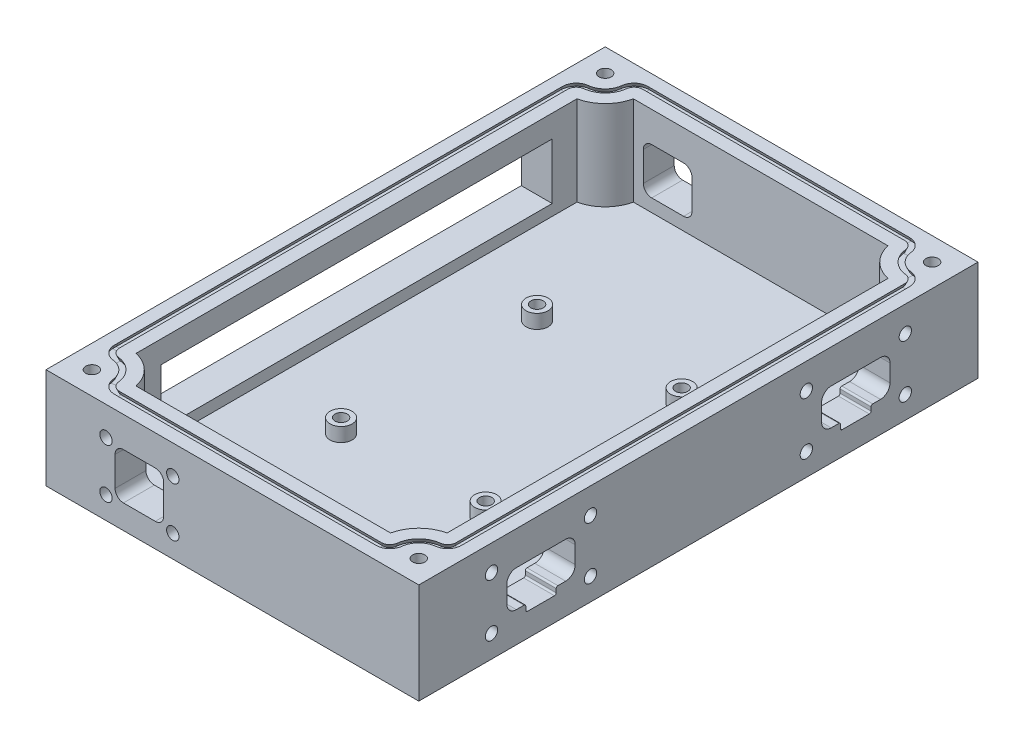
SolidWorks part; units mm, degrees
note: The reader was unsure of these and kept them because the rebuilt part matched: shared geometry of "Sketch5<2>", "Sketch6<2>".
ref_plane "Front Plane" through (0, 0, 0) normal (0, 0, 1) x (1, 0, 0)
ref_plane "Top Plane" through (0, 0, 0) normal (0, 1, 0) x (1, 0, 0)
ref_plane "Right Plane" through (0, 0, 0) normal (1, 0, 0) x (0, 0, -1)
sketch "Sketch1" plane through (0, 0, 0) normal (0, 1, 0) x (1, 0, 0)
  line L1 (0, 0) -> (169.3418, 0)
  line L2 (0, 0) -> (0, 254)
  line L3 (0, 254) -> (169.3418, 254)
  line L4 (169.3418, 0) -> (169.3418, 254)
  dimension "D1" = 169.3418
  dimension "D2" = 254
extrude "Boss-Extrude1" add sketch "Sketch1" along normal blind 45.72
sketch "12 pin hole" [suppressed] plane through (254, 0, 0) normal (1, 0, 0) x (0, 0, -1)
  line L8 (50.8, 10.16) -> (95.758, 10.16) construction
  line L9 (50.8, 10.16) -> (50.8, 34.036) construction
  line L10 (50.8, 34.036) -> (95.758, 34.036) construction
  line L11 (95.758, 10.16) -> (95.758, 34.036) construction
  line L12 (55.7357, 28.956) -> (54.2925, 28.956)
  line L13 (52.7685, 27.432) -> (52.7685, 16.764)
  line L14 (54.2925, 15.24) -> (55.7357, 15.24)
  line L16 (90.087, 29.972) -> (92.2655, 29.972)
  line L17 (93.7895, 28.448) -> (93.7895, 15.748)
  line L18 (92.2655, 14.224) -> (90.087, 14.224)
  line L21 (62.4205, 25.654) -> (84.1375, 25.654) construction
  line L22 (62.4205, 25.654) -> (62.4205, 18.542) construction
  line L23 (62.4205, 18.542) -> (84.1375, 18.542) construction
  line L24 (84.1375, 25.654) -> (84.1375, 18.542) construction
  line L25 (62.4205, 32.7152) -> (84.1375, 32.7152)
  line L26 (62.4205, 11.4808) -> (84.1375, 11.4808)
  line L27 (52.7685, 22.098) -> (50.8, 22.098) construction
  line L28 (93.7895, 22.098) -> (95.758, 22.098) construction
  arc A4 (62.4205, 32.7152) -> (56.3868, 29.3222) centre (62.4205, 25.654) ccw
  arc A5 (89.5075, 30.2392) -> (84.1375, 32.7152) centre (84.1375, 25.654) ccw
  arc A6 (62.4205, 11.4808) -> (56.3868, 14.8738) centre (62.4205, 18.542) cw
  arc A7 (89.5075, 13.9568) -> (84.1375, 11.4808) centre (84.1375, 18.542) cw
  arc A8 (90.087, 29.972) -> (89.5075, 30.2392) centre (90.087, 30.734) cw
  arc A9 (90.087, 14.224) -> (89.5075, 13.9568) centre (90.087, 13.462) ccw
  arc A10 (55.7357, 15.24) -> (56.3868, 14.8738) centre (55.7357, 14.478) cw
  arc A11 (55.7357, 28.956) -> (56.3868, 29.3222) centre (55.7357, 29.718) ccw
  arc A12 (92.2655, 29.972) -> (93.7895, 28.448) centre (92.2655, 28.448) cw
  arc A13 (93.7895, 15.748) -> (92.2655, 14.224) centre (92.2655, 15.748) cw
  arc A14 (52.7685, 16.764) -> (54.2925, 15.24) centre (54.2925, 16.764) ccw
  arc A15 (54.2925, 28.956) -> (52.7685, 27.432) centre (54.2925, 27.432) ccw
  point P25 (50.8, 22.098)
  point P28 (52.7685, 22.098)
  point P29 (93.7895, 22.098)
  point P34 (62.4205, 22.098)
  point P35 (84.1375, 22.098)
  point P44 (73.279, 10.16)
  point P46 (73.279, 11.4808)
  point P59 (93.7895, 29.972)
  point P62 (93.7895, 14.224)
  point P65 (52.7685, 15.24)
  point P68 (52.7685, 28.956)
  dimension "D4" = 41.021
  dimension "D5" = 15.748
  dimension "D11" = 7.0612
  dimension "D12" = 0.762
  dimension "D13" = 1.524
  dimension "D1" = 44.958
  dimension "D2" = 23.876
  dimension "D8" = 13.716
  dimension "D9" = 21.2344
  dimension "D10" = 21.717
sketch "Sketch2" plane through (0, 45.72, 0) normal (0, 1, 0) x (1, 0, 0)
  line L0 (84.6709, 14.0292) -> (84.6709, 0) construction
  line L5 (0, 10.42) -> (10.42, 10.42) construction
  line L6 (14.0292, 239.9708) -> (155.3126, 239.9708)
  line L7 (10.42, 10.42) -> (10.42, 0) construction
  line L16 (14.0292, 239.9708) -> (14.0292, 14.0292)
  line L17 (14.0292, 14.0292) -> (155.3126, 14.0292)
  line L18 (155.3126, 239.9708) -> (155.3126, 14.0292)
  line L19 (0, 0) -> (169.3418, 0) construction
  line L20 (158.9218, 0) -> (158.9218, 10.42) construction
  line L21 (14.0292, 127) -> (0, 127) construction
  line L22 (0, 254) -> (0, 0) construction
  line L23 (158.9218, 10.42) -> (169.3418, 10.42) construction
  line L24 (169.3418, 0) -> (169.3418, 254) construction
  line L25 (25.2202, 246.9854) -> (144.1216, 246.9854)
  line L38 (7.0146, 228.7798) -> (7.0146, 25.2202)
  line L47 (25.2202, 7.0146) -> (144.1216, 7.0146)
  line L48 (162.3272, 228.7798) -> (162.3272, 25.2202)
  line L49 (169.3418, 243.58) -> (158.9218, 243.58) construction
  line L50 (158.9218, 243.58) -> (158.9218, 254) construction
  line L51 (169.3418, 254) -> (0, 254) construction
  line L52 (0, 243.58) -> (10.42, 243.58) construction
  line L53 (10.42, 243.58) -> (10.42, 254) construction
  line L54 (10.42, 10.42) -> (17.36, 17.36) construction
  line L55 (17.36, 17.36) -> (22.3201, 22.3201) construction
  line L56 (158.9218, 10.42) -> (151.9818, 17.36) construction
  line L57 (151.9818, 17.36) -> (147.0217, 22.3201) construction
  line L58 (158.9218, 243.58) -> (151.9818, 236.64) construction
  line L59 (151.9818, 236.64) -> (147.0217, 231.6799) construction
  line L60 (10.42, 243.58) -> (17.36, 236.64) construction
  line L61 (17.36, 236.64) -> (22.3201, 231.6799) construction
  line L62 (155.3126, 127) -> (169.3418, 127) construction
  line L63 (84.6709, 239.9708) -> (84.6709, 254) construction
  arc A13 (26.8577, 14.0292) -> (14.0292, 26.8577) centre (10.42, 10.42) ccw
  arc A14 (14.0292, 227.1423) -> (26.8577, 239.9708) centre (10.42, 243.58) ccw
  arc A15 (142.4841, 239.9708) -> (155.3126, 227.1423) centre (158.9218, 243.58) ccw
  arc A16 (155.3126, 26.8577) -> (142.4841, 14.0292) centre (158.9218, 10.42) ccw
  arc A17 (157.8183, 20.1724) -> (149.1694, 11.5235) centre (158.9218, 10.42) ccw
  arc A18 (149.1694, 242.4765) -> (157.8183, 233.8276) centre (158.9218, 243.58) ccw
  arc A19 (11.5235, 233.8276) -> (20.1724, 242.4765) centre (10.42, 243.58) ccw
  arc A20 (20.1724, 11.5235) -> (11.5235, 20.1724) centre (10.42, 10.42) ccw
  arc A21 (25.2202, 7.0146) -> (20.1724, 11.5235) centre (25.2202, 12.0946) cw
  arc A22 (149.1694, 11.5235) -> (144.1216, 7.0146) centre (144.1216, 12.0946) cw
  arc A23 (162.3272, 25.2202) -> (157.8183, 20.1724) centre (157.2472, 25.2202) cw
  arc A24 (162.3272, 228.7798) -> (157.8183, 233.8276) centre (157.2472, 228.7798) ccw
  arc A25 (149.1694, 242.4765) -> (144.1216, 246.9854) centre (144.1216, 241.9054) ccw
  arc A26 (25.2202, 246.9854) -> (20.1724, 242.4765) centre (25.2202, 241.9054) ccw
  arc A27 (11.5235, 233.8276) -> (7.0146, 228.7798) centre (12.0946, 228.7798) ccw
  arc A28 (11.5235, 20.1724) -> (7.0146, 25.2202) centre (12.0946, 25.2202) cw
  point P12 (84.6709, 7.0146)
  point P17 (84.6709, 7.0146)
  point P18 (7.0146, 127)
  point P85 (84.6709, 246.9854)
  point P86 (84.6709, 246.9854)
  point P87 (162.3272, 127)
  point P88 (162.3272, 127)
  point P89 (10.42, 243.58)
  point P90 (7.0146, 127)
  point P91 (10.42, 10.42)
  point P92 (158.9218, 10.42)
  point P93 (158.9218, 243.58)
  dimension "D2" = 9.8146
  dimension "D1" = 7.0146
  dimension "D3" = 10.42
  dimension "D4" = 7.0146
extrude "Cut-Extrude1" cut sketch "Sketch2" against normal offset from surface (40.64 mm away) 5.08
ref_plane "groove plane" through (14.0292, 45.72, -26.8577) normal (0, 0, 1) x (1, 0, 0)
sketch "Sketch3" plane through (0, 45.72, 0) normal (0, 1, 0) x (1, 0, 0)
  line L64 (25.2202, 246.9854) -> (144.1216, 246.9854) construction
  line L65 (162.3272, 228.7798) -> (162.3272, 25.2202) construction
  line L66 (25.2202, 7.0146) -> (144.1216, 7.0146) construction
  line L67 (7.0146, 228.7798) -> (7.0146, 25.2202) construction
  line L68 (25.2202, 246.9854) -> (144.1216, 246.9854)
  line L69 (162.3272, 228.7798) -> (162.3272, 25.2202)
  line L70 (25.2202, 7.0146) -> (144.1216, 7.0146)
  line L71 (7.0146, 228.7798) -> (7.0146, 25.2202)
  arc A40 (149.1694, 242.4765) -> (144.1216, 246.9854) centre (144.1216, 241.9054) ccw construction
  arc A41 (149.1694, 242.4765) -> (157.8183, 233.8276) centre (158.9218, 243.58) ccw construction
  arc A42 (162.3272, 228.7798) -> (157.8183, 233.8276) centre (157.2472, 228.7798) ccw construction
  arc A43 (157.8183, 20.1724) -> (162.3272, 25.2202) centre (157.2472, 25.2202) ccw construction
  arc A44 (157.8183, 20.1724) -> (149.1694, 11.5235) centre (158.9218, 10.42) ccw construction
  arc A45 (144.1216, 7.0146) -> (149.1694, 11.5235) centre (144.1216, 12.0946) ccw construction
  arc A46 (20.1724, 11.5235) -> (25.2202, 7.0146) centre (25.2202, 12.0946) ccw construction
  arc A47 (20.1724, 11.5235) -> (11.5235, 20.1724) centre (10.42, 10.42) ccw construction
  arc A48 (7.0146, 25.2202) -> (11.5235, 20.1724) centre (12.0946, 25.2202) ccw construction
  arc A49 (11.5235, 233.8276) -> (7.0146, 228.7798) centre (12.0946, 228.7798) ccw construction
  arc A50 (11.5235, 233.8276) -> (20.1724, 242.4765) centre (10.42, 243.58) ccw construction
  arc A51 (25.2202, 246.9854) -> (20.1724, 242.4765) centre (25.2202, 241.9054) ccw construction
  arc A52 (149.1694, 242.4765) -> (144.1216, 246.9854) centre (144.1216, 241.9054) ccw
  arc A53 (149.1694, 242.4765) -> (157.8183, 233.8276) centre (158.9218, 243.58) ccw
  arc A54 (162.3272, 228.7798) -> (157.8183, 233.8276) centre (157.2472, 228.7798) ccw
  arc A55 (157.8183, 20.1724) -> (162.3272, 25.2202) centre (157.2472, 25.2202) ccw
  arc A56 (157.8183, 20.1724) -> (149.1694, 11.5235) centre (158.9218, 10.42) ccw
  arc A57 (144.1216, 7.0146) -> (149.1694, 11.5235) centre (144.1216, 12.0946) ccw
  arc A58 (20.1724, 11.5235) -> (25.2202, 7.0146) centre (25.2202, 12.0946) ccw
  arc A59 (20.1724, 11.5235) -> (11.5235, 20.1724) centre (10.42, 10.42) ccw
  arc A60 (7.0146, 25.2202) -> (11.5235, 20.1724) centre (12.0946, 25.2202) ccw
  arc A61 (11.5235, 233.8276) -> (7.0146, 228.7798) centre (12.0946, 228.7798) ccw
  arc A62 (11.5235, 233.8276) -> (20.1724, 242.4765) centre (10.42, 243.58) ccw
  arc A63 (25.2202, 246.9854) -> (20.1724, 242.4765) centre (25.2202, 241.9054) ccw
sketch "Sketch4" plane through (6.1853, 0, -26.8577) normal (0, 0, 1) x (1, 0, 0)
  line L0 (-0.3137, 45.72) -> (-1.1053, 43.942)
  line L1 (1.9723, 45.72) -> (2.764, 43.942)
  line L2 (-1.1053, 43.942) -> (2.764, 43.942)
  line L5 (-0.3137, 45.72) -> (1.9723, 45.72)
  point P5 (0.8293, 45.72)
  dimension "D1" = 1.778
  dimension "D3" = 66
  dimension "D4" = 66
  dimension "D2" = 3.8692
sweep "Cut-Sweep2" cut profiles "Sketch4" path "Sketch3"
sketch "Sketch14" plane through (0, 45.72, 0) normal (0, 1, 0) x (1, 0, 0)
  circle A0 centre (10.42, 243.58) radius 2.8
  circle A1 centre (158.9218, 243.58) radius 2.8
  circle A2 centre (158.9218, 10.42) radius 2.8
  circle A3 centre (10.42, 10.42) radius 2.8
  dimension "D1" = 5.6
extrude "Cut-Extrude11" cut sketch "Sketch14" against normal blind 5.5
sketch "Sketch13" plane through (169.3418, 0, 0) normal (1, 0, 0) x (0, 0, -1)
  line L0 (33.02, 10.16) -> (33.02, 0) construction
  line L1 (0, 0) -> (254, 0) construction
  line L2 (33.02, 10.16) -> (0, 10.16) construction
  line L3 (0, 45.72) -> (0, 0) construction
  line L4 (220.98, 0) -> (220.98, 10.16) construction
  line L5 (220.98, 10.16) -> (254, 10.16) construction
  line L6 (254, 45.72) -> (254, 0) construction
  line B0 (48.5902, 13.0937) -> (48.5902, 11.4173)
  line B1 (33.02, 34.036) -> (77.978, 34.036) construction
  line B2 (33.02, 34.036) -> (33.02, 10.16) construction
  line B3 (33.02, 10.16) -> (77.978, 10.16) construction
  line B4 (77.978, 34.036) -> (77.978, 10.16) construction
  line B5 (44.2976, 30.3403) -> (66.7004, 30.3403)
  line B6 (39.9542, 25.9969) -> (39.9542, 18.1991)
  line B7 (44.2976, 13.8557) -> (47.8282, 13.8557)
  line B8 (71.0438, 25.9969) -> (71.0438, 18.1991)
  line B9 (39.9542, 30.3403) -> (71.0438, 13.8557) construction
  line B10 (39.9542, 13.8557) -> (71.0438, 30.3403) construction
  line B11 (49.3522, 10.6553) -> (61.6458, 10.6553)
  line B12 (62.4078, 11.4173) -> (62.4078, 13.0937)
  line B13 (63.1698, 13.8557) -> (66.7004, 13.8557)
  arc B14 (66.7004, 13.8557) -> (71.0438, 18.1991) centre (66.7004, 18.1991) ccw
  arc B15 (39.9542, 18.1991) -> (44.2976, 13.8557) centre (44.2976, 18.1991) ccw
  arc B16 (66.7004, 30.3403) -> (71.0438, 25.9969) centre (66.7004, 25.9969) cw
  arc B17 (44.2976, 30.3403) -> (39.9542, 25.9969) centre (44.2976, 25.9969) ccw
  arc B18 (62.4078, 13.0937) -> (63.1698, 13.8557) centre (63.1698, 13.0937) cw
  arc B19 (61.6458, 10.6553) -> (62.4078, 11.4173) centre (61.6458, 11.4173) ccw
  arc B20 (48.5902, 11.4173) -> (49.3522, 10.6553) centre (49.3522, 11.4173) ccw
  arc B21 (48.5902, 13.0937) -> (47.8282, 13.8557) centre (47.8282, 13.0937) ccw
  line B22 (191.5922, 13.0937) -> (191.5922, 11.4173)
  line B23 (176.022, 34.036) -> (220.98, 34.036) construction
  line B24 (176.022, 34.036) -> (176.022, 10.16) construction
  line B25 (176.022, 10.16) -> (220.98, 10.16) construction
  line B26 (220.98, 34.036) -> (220.98, 10.16) construction
  line B27 (187.2996, 30.3403) -> (209.7024, 30.3403)
  line B28 (182.9562, 25.9969) -> (182.9562, 18.1991)
  line B29 (187.2996, 13.8557) -> (190.8302, 13.8557)
  line B30 (214.0458, 25.9969) -> (214.0458, 18.1991)
  line B31 (182.9562, 30.3403) -> (214.0458, 13.8557) construction
  line B32 (182.9562, 13.8557) -> (214.0458, 30.3403) construction
  line B33 (192.3542, 10.6553) -> (204.6478, 10.6553)
  line B34 (205.4098, 11.4173) -> (205.4098, 13.0937)
  line B35 (206.1718, 13.8557) -> (209.7024, 13.8557)
  arc B36 (209.7024, 13.8557) -> (214.0458, 18.1991) centre (209.7024, 18.1991) ccw
  arc B37 (182.9562, 18.1991) -> (187.2996, 13.8557) centre (187.2996, 18.1991) ccw
  arc B38 (209.7024, 30.3403) -> (214.0458, 25.9969) centre (209.7024, 25.9969) cw
  arc B39 (187.2996, 30.3403) -> (182.9562, 25.9969) centre (187.2996, 25.9969) ccw
  arc B40 (205.4098, 13.0937) -> (206.1718, 13.8557) centre (206.1718, 13.0937) cw
  arc B41 (204.6478, 10.6553) -> (205.4098, 11.4173) centre (204.6478, 11.4173) ccw
  arc B42 (191.5922, 11.4173) -> (192.3542, 10.6553) centre (192.3542, 11.4173) ccw
  arc B43 (191.5922, 13.0937) -> (190.8302, 13.8557) centre (190.8302, 13.0937) ccw
  dimension "D1" = 33.02
  dimension "D2" = 10.16
sketch_block_instance "Block7-3"
sketch_block "Block7" parameters "D6"=4.3434, "D7"=0.762, "D1"=44.958, "D2"=23.876, "D3"=31.0896, "D4"=16.4846, "D5"=19.685
sketch_block_instance "Block7-4"
extrude "Cut-Extrude10" cut sketch "Sketch13" against normal up to next
sketch "12 pin mount" plane through (169.3418, 0, 0) normal (1, 0, 0) x (0, 0, -1)
  circle A0 centre (77.978, 34.036) radius 2.8
  circle A1 centre (176.022, 10.16) radius 2.8
  circle A2 centre (33.02, 10.16) radius 2.8
  circle A3 centre (77.978, 10.16) radius 2.8
  circle A5 centre (220.98, 34.036) radius 2.8
  circle A6 centre (220.98, 10.16) radius 2.8
  circle A7 centre (176.022, 34.036) radius 2.8
  circle A8 centre (33.02, 34.036) radius 2.8
  dimension "D1" = 5.6
extrude "Cut-Extrude3" cut sketch "12 pin mount" against normal blind 5.5
sketch "4 pin connector" plane through (0, 0, 0) normal (0, 0, 1) x (1, 0, 0)
  line L0 (57.5818, 0) -> (57.5818, 10.16) construction
  line L1 (0, 0) -> (169.3418, 0) construction
  line L2 (57.5818, 10.16) -> (169.3418, 10.16) construction
  line L3 (169.3418, 45.72) -> (169.3418, 0) construction
  line L5 (27.2288, 32.6136) -> (57.5818, 32.6136) construction
  line L6 (27.2288, 32.6136) -> (27.2288, 10.16) construction
  line L7 (27.2288, 10.16) -> (57.5818, 10.16) construction
  line L8 (57.5818, 32.6136) -> (57.5818, 10.16) construction
  line L9 (35.1663, 31.877) -> (49.6443, 31.877)
  line L10 (31.3563, 28.067) -> (31.3563, 14.7066)
  line L11 (35.1663, 10.8966) -> (49.6443, 10.8966)
  line L12 (53.4543, 28.067) -> (53.4543, 14.7066)
  line L13 (42.4053, 10.8966) -> (42.4053, 31.877) construction
  line L14 (31.3563, 21.3868) -> (53.4543, 21.3868) construction
  arc A0 (49.6443, 31.877) -> (53.4543, 28.067) centre (49.6443, 28.067) cw
  arc A1 (49.6443, 10.8966) -> (53.4543, 14.7066) centre (49.6443, 14.7066) ccw
  arc A2 (31.3563, 14.7066) -> (35.1663, 10.8966) centre (35.1663, 14.7066) ccw
  arc A3 (35.1663, 31.877) -> (31.3563, 28.067) centre (35.1663, 28.067) ccw
  point P4 (42.4053, 21.3868)
  point P12 (42.4053, 10.16)
  point P15 (57.5818, 21.3868)
  point P20 (53.4543, 31.877)
  point P24 (53.4543, 10.8966)
  point P29 (31.3563, 31.877)
  dimension "D1" = 22.098
  dimension "D7" = 3.81
  dimension "D2" = 22.4536
  dimension "D3" = 30.353
  dimension "D4" = 10.16
  dimension "D5" = 111.76
  dimension "D6" = 20.9804
extrude "Cut-Extrude5" cut sketch "4 pin connector" against normal up to next
extrude "Cut-Extrude6" cut sketch "Sketch5<2>" along normal up to next from surface
sketch "Sketch5<2>" plane through (0, 0, 0) normal (0, 0, 1) x (1, 0, 0) same geometry as "4 pin connector"
sketch "Sketch6" plane through (0, 0, 0) normal (0, 0, 1) x (1, 0, 0)
  circle A0 centre (57.5818, 32.6136) radius 2.8
  circle A1 centre (57.5818, 10.16) radius 2.8
  circle A2 centre (27.2288, 10.16) radius 2.8
  circle A3 centre (27.2288, 32.6136) radius 2.8
  dimension "D1" = 5.6
extrude "Cut-Extrude7" cut sketch "Sketch6" against normal blind 5.5
extrude "Cut-Extrude8" cut sketch "Sketch6<2>" along normal blind 5.5 from surface at -254 starting at face at (42.4053, 21.3868, -254)
sketch "Sketch6<2>" plane through (0, 0, 0) normal (0, 0, 1) x (1, 0, 0) same geometry as "Sketch6"
sketch "Sketch7" plane through (0, 5.08, 0) normal (0, 1, 0) x (1, 0, 0)
  line L0 (117.2126, 127) -> (155.3126, 127) construction
  line L5 (117.2126, 82.485) -> (51.5526, 82.485) construction
  line L6 (117.2126, 82.485) -> (117.2126, 171.515) construction
  line L7 (117.2126, 171.515) -> (51.5526, 171.515) construction
  line L8 (51.5526, 82.485) -> (51.5526, 171.515) construction
  circle A0 centre (51.5526, 82.485) radius 5
  circle A1 centre (117.2126, 82.485) radius 5
  circle A2 centre (117.2126, 171.515) radius 5
  circle A3 centre (51.5526, 171.515) radius 5
  dimension "D1" = 10
  dimension "D2" = 89.03
  dimension "D3" = 65.66
  dimension "D4" = 38.1
sketch "Sketch8" plane through (0, 5.08, 0) normal (0, 1, 0) x (1, 0, 0)
  circle A0 centre (51.5526, 171.515) radius 2.8
  circle A1 centre (117.2126, 171.515) radius 2.8
  circle A2 centre (117.2126, 82.485) radius 2.8
  circle A3 centre (51.5526, 82.485) radius 2.8
  dimension "D1" = 5.6
extrude "Boss-Extrude2" add sketch "Sketch7" along normal blind 6.35
extrude "Cut-Extrude9" cut sketch "Sketch8" against normal blind 5.5 from surface at 6.35 starting at face at (117.2126, 11.43, -77.485)
sketch "Sketch18" plane through (0, 0, 0) normal (-1, 0, 0) x (0, 0, 1)
  line L0 (-127, 10.16) -> (-127, 0) construction
  line L1 (-215.9, 35.56) -> (-38.1, 35.56)
  line L2 (-215.9, 35.56) -> (-215.9, 10.16)
  line L3 (-215.9, 10.16) -> (-38.1, 10.16)
  line L4 (-38.1, 35.56) -> (-38.1, 10.16)
  line L5 (-254, 0) -> (0, 0) construction
  line L6 (-38.1, 22.86) -> (0, 22.86) construction
  line L7 (0, 45.72) -> (0, 0) construction
  dimension "D1" = 25.4
  dimension "D2" = 177.8
extrude "Cut-Extrude12" cut sketch "Sketch18" against normal up to next contours L2 L1 L4 L3
equation "\"M4 insert  width\"= 5.6mm"
equation "\"M4 insert  depth\"= 5.5mm"
equation "\"depth\"=0.1"
equation "\"groove bottom\"= 0.15233202in"
equation "\"D2@Sketch4\"=\"groove bottom\""
equation "\"D1@Sketch2\"=\"groove bottom\"/2+0.2"
equation "\"D3@Sketch2\"=\"M4 insert  width\"/2+0.3"
